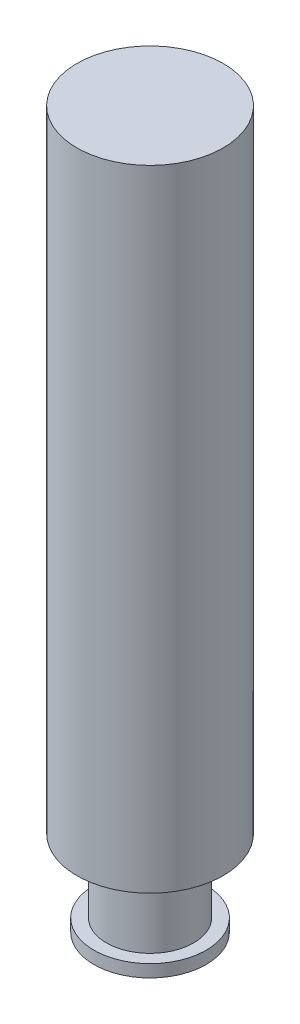
SolidWorks part; units mm, degrees
ref_plane "Front" through (0, 0, 0) normal (0, 0, 1) x (1, 0, 0)
ref_plane "Top" through (0, 0, 0) normal (0, 1, 0) x (1, 0, 0)
ref_plane "Right" through (0, 0, 0) normal (1, 0, 0) x (0, 0, -1)
sketch "Sketch1" plane through (-15.2749, 30.2146, 34.3702) normal (0.7588, 0, 0.6513) x (-0.6513, 0, 0.7588)
  line L0 (-0.7943, 0.007) -> (-0.7943, 2.2852) construction
  line L1 (0.5385, -0.016) -> (-0.7943, -0.016)
  line L2 (-0.7943, 12.7963) -> (-0.7943, -0.016)
  line L5 (0.5385, -0.016) -> (0.5385, 11.466)
  line L6 (0.5385, 11.466) -> (-0.0006, 11.466)
  line L7 (-0.0006, 11.684) -> (-0.0006, 0.007) construction
  line L8 (-0.0006, 11.466) -> (-0.0006, 12.7963)
  line L9 (-0.7943, -0.1737) -> (-0.7943, -1.5665) construction
  line L10 (-0.0006, 12.7963) -> (0.2284, 12.7963)
  line L11 (0.2284, 12.7963) -> (0.2284, 13.0227)
  line L12 (0.2284, 13.0227) -> (-0.7943, 13.0227)
  line L13 (-0.7943, 13.0227) -> (-0.7943, 12.7963)
revolve "Revolve1" add sketch "Sketch1" angle 360 about L9
sketch "Sketch5" plane through (0, 30.2306, 0) normal (0, 1, 0) x (1, 0, 0)
  line L0 (-23.5413, -44.0015) -> (-15.2745, -34.3698) construction
  line L1 (-13.8895, -32.7561) -> (-15.6256, -32.7561)
  line L2 (-13.8895, -32.7561) -> (-13.8895, -34.7788) construction
  line L3 (-13.8895, -34.7788) -> (-15.6256, -34.7788)
  line L4 (-15.6256, -32.7561) -> (-15.6256, -34.7788)
  line L5 (-13.8895, -32.7561) -> (-15.6256, -34.7788) construction
  line L6 (-13.8895, -34.7788) -> (-15.6256, -32.7561) construction
  line L7 (-13.8895, -32.7561) -> (1.5212, -32.7561)
  line L8 (-13.8895, -34.7788) -> (1.5212, -34.7788)
  line L9 (1.5212, -34.7788) -> (1.5212, -32.7561)
  line L10 (-14.7575, -33.7675) -> (4.4862, -33.7675) construction
  circle A0 centre (0, -33.7675) radius 0.75
  circle A1 centre (-14.7575, -33.7675) radius 1.3328
  circle A2 centre (-14.7575, -33.7675) radius 1.3328 construction
  dimension "D2" = 1.5
  dimension "D1" = 0
